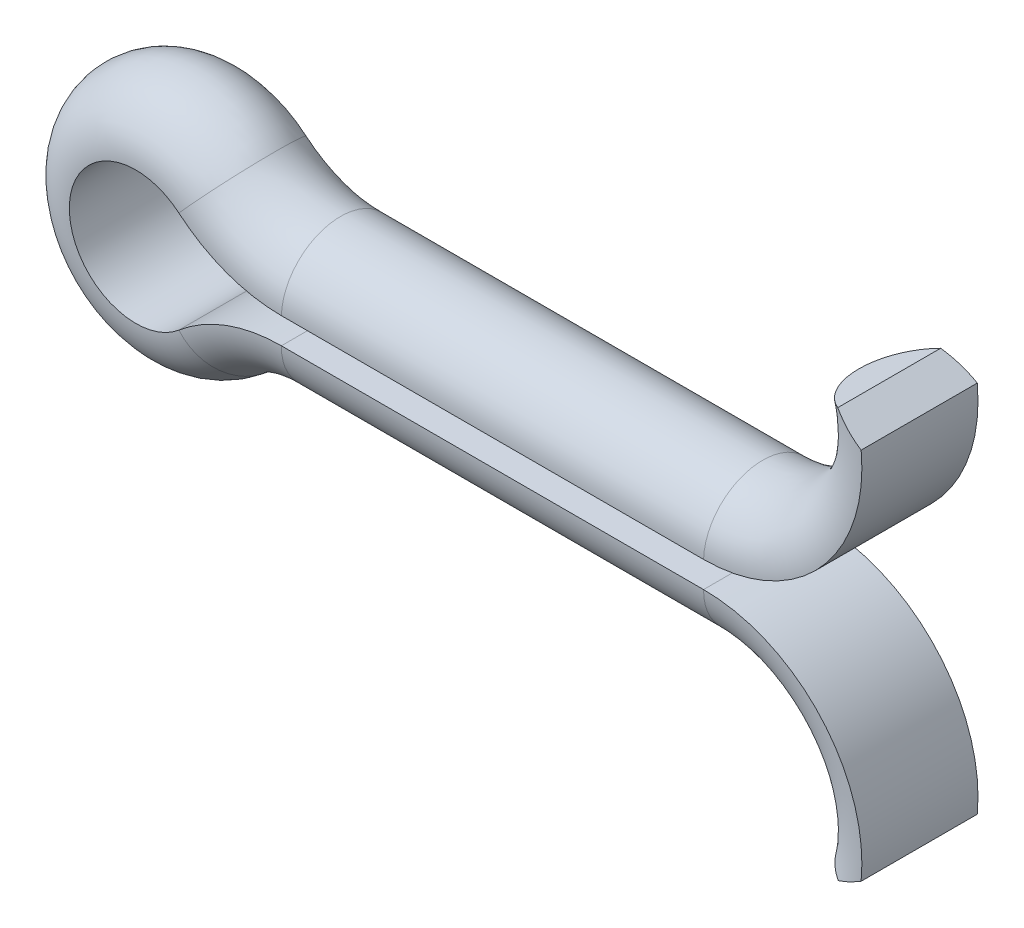
SolidWorks part; units mm, degrees
ref_plane "Front Plane" through (0, 0, 0) normal (0, 0, 1) x (1, 0, 0)
ref_plane "Top Plane" through (0, 0, 0) normal (0, 1, 0) x (1, 0, 0)
ref_plane "Right Plane" through (0, 0, 0) normal (1, 0, 0) x (0, 0, -1)
sketch "Sketch2" plane through (0, 0, 0) normal (0, 0, 1) x (1, 0, 0)
  line L0 (11.8027, 0) -> (-2.2752, 0) construction
  line L1 (2.7574, 0.2472) -> (10.7574, 0.2472)
  line L2 (2.7574, -0.2472) -> (10.7574, -0.2472)
  arc A0 (0.8156, -0.9604) -> (0.8156, 0.9604) centre (0, 0) cw
  arc A1 (0.8156, 0.9604) -> (2.7574, 0.2472) centre (2.7574, 3.2472) ccw
  arc A2 (0.8156, -0.9604) -> (2.7574, -0.2472) centre (2.7574, -3.2472) cw
  arc A3 (10.7574, 0.2472) -> (13.6614, 4) centre (10.7574, 3.2472) ccw
  arc A4 (10.7574, -0.2472) -> (13.6614, -4) centre (10.7574, -3.2472) cw
  point P16 (-0.6, 0)
  dimension "D1" = 1.26
  dimension "D2" = 3
  dimension "D3" = 8
  dimension "D4" = 3
  dimension "D5" = 4
  dimension "D6" = 0.6
ref_plane "Plane1" through (-0.0438, -0.156, 0) normal (-0.2701, -0.9628, 0) x (-0.9628, 0.2701, 0)
sketch "Sketch3" plane through (-0.0438, -0.156, 0) normal (-0.2701, -0.9628, 0) x (-0.9628, 0.2701, 0)
  line L0 (-14.2341, 0) -> (-14.2341, 1.1)
  line L1 (-14.2341, 0) -> (-10.4245, 0) construction
  line L2 (-14.2341, -1.1) -> (-14.2341, 0)
  arc A0 (-14.2341, 1.1) -> (-14.2341, -1.1) centre (-14.2441, 0) cw
  point P6 (-13.1441, 0)
  dimension "D1" = 2.2
  dimension "D2" = 1.09
sweep "Sweep1" add profiles "Sketch3" path "Sketch2"
chamfer "Chamfer1" distance 0.5 angle 45 2 edges at (13.6614, -4, 0) (13.6614, 4, 0)
